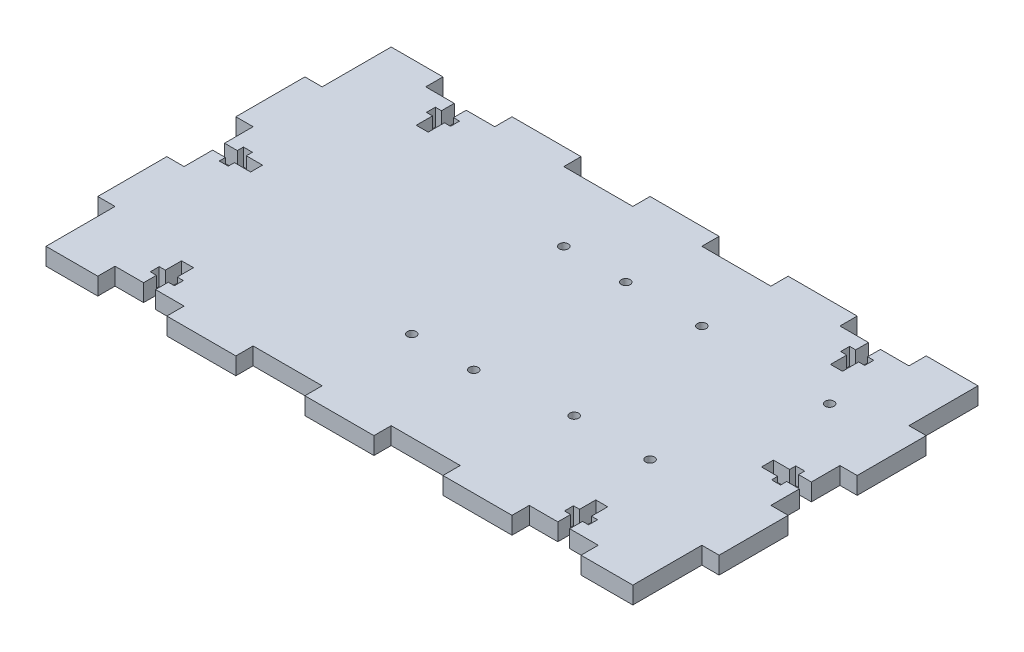
SolidWorks part; units mm, degrees
ref_plane "Front Plane" through (0, 0, 0) normal (0, 0, 1) x (1, 0, 0)
ref_plane "Top Plane" through (0, 0, 0) normal (0, 1, 0) x (1, 0, 0)
ref_plane "Right Plane" through (0, 0, 0) normal (1, 0, 0) x (0, 0, -1)
sketch "Sketch1" plane through (0, 0, 0) normal (0, 1, 0) x (1, 0, 0)
  line L1 (0, 0) -> (228.6, 0)
  line L2 (0, 0) -> (0, 127)
  line L3 (0, 127) -> (228.6, 127)
  line L4 (228.6, 0) -> (228.6, 127)
  dimension "D1" = 127
  dimension "D2" = 228.6
extrude "Boss-Extrude1" add sketch "Sketch1" along normal blind 6.35
sketch "Sketch2" plane through (0, 6.35, 0) normal (0, 1, 0) x (1, 0, 0)
  line L1 (0, 127) -> (6.35, 127)
  line L2 (0, 127) -> (0, 101.6)
  line L3 (0, 101.6) -> (6.35, 101.6)
  line L4 (6.35, 127) -> (6.35, 101.6)
  dimension "D1" = 25.4
  dimension "D2" = 6.35
extrude "Cut-Extrude1" cut sketch "Sketch2" against normal blind 6.35
pattern_linear "LPattern1" count 3 spacing 50.8 along (0, 0, 1) count 2 spacing 222.25 along (1, 0, 0) of "Cut-Extrude1"
sketch "Sketch3" plane through (0, 6.35, 0) normal (0, 1, 0) x (1, 0, 0)
  line L0 (6.35, 0) -> (222.25, 0) construction
  line L1 (25.4, 0) -> (50.8, 0)
  line L2 (25.4, 0) -> (25.4, 6.35)
  line L3 (25.4, 6.35) -> (50.8, 6.35)
  line L4 (50.8, 0) -> (50.8, 6.35)
  line L5 (0, 50.8) -> (0, 25.4) construction
  dimension "D1" = 25.4
  dimension "D2" = 6.35
  dimension "D3" = 25.4
extrude "Cut-Extrude2" cut sketch "Sketch3" against normal blind 6.35
pattern_linear "LPattern2" count 4 spacing 50.8 along (1, 0, 0) count 2 spacing 120.65 along (0, 0, -1) of "Cut-Extrude2"
ref_plane "Plane1" through (0, 0, -63.5) normal (0, 0, 1) x (1, 0, 0)
ref_plane "Plane2" through (114.3, 0, 0) normal (1, 0, 0) x (0, 0, -1)
sketch "Sketch4" plane through (0, 6.35, 0) normal (0, 1, 0) x (1, 0, 0)
  line L0 (222.25, 76.2) -> (222.25, 50.8) construction
  line L1 (222.25, 65.6971) -> (208.28, 65.6971)
  line L2 (222.25, 65.6971) -> (222.25, 61.3029)
  line L3 (222.25, 61.3029) -> (208.28, 61.3029)
  line L4 (208.28, 65.6971) -> (208.28, 61.3029)
  line L5 (228.6, 76.2) -> (222.25, 76.2) construction
  line L7 (214.249, 67.945) -> (217.551, 67.945)
  line L8 (214.249, 67.945) -> (214.249, 59.055)
  line L9 (214.249, 59.055) -> (217.551, 59.055)
  line L10 (217.551, 67.945) -> (217.551, 59.055)
  point P6 (222.25, 63.5)
  point P13 (215.9, 59.055)
  point P14 (217.551, 63.5)
  dimension "D1" = 13.97
  dimension "D2" = 4.3942
  dimension "D3" = 12.7
  dimension "D4" = 3.302
  dimension "D5" = 6.35
  dimension "D6" = 8.89
  dimension "D7" = 12.7
extrude "Cut-Extrude3" cut sketch "Sketch4" against normal blind 8.89 contours L1 L4 L3 L2 | L7 L10 L9 L8
mirror "Mirror1" about plane through (114.3, 0, 0) normal (1, 0, 0) of "Cut-Extrude3"
sketch "Sketch5" plane through (0, 6.35, 0) normal (0, 1, 0) x (1, 0, 0)
  line L0 (50.8, 6.35) -> (25.4, 6.35) construction
  line L1 (35.9029, 6.35) -> (40.2971, 6.35)
  line L2 (35.9029, 6.35) -> (35.9029, 20.32)
  line L3 (35.9029, 20.32) -> (40.2971, 20.32)
  line L4 (40.2971, 6.35) -> (40.2971, 20.32)
  line L5 (50.8, 0) -> (50.8, 6.35) construction
  line L6 (33.655, 14.351) -> (42.545, 14.351)
  line L7 (33.655, 14.351) -> (33.655, 11.049)
  line L8 (33.655, 11.049) -> (42.545, 11.049)
  line L9 (42.545, 14.351) -> (42.545, 11.049)
  point P6 (38.1, 20.32)
  point P12 (38.1, 11.049)
  point P15 (42.545, 12.7)
  dimension "D1" = 13.97
  dimension "D2" = 4.3942
  dimension "D3" = 12.7
  dimension "D4" = 3.302
  dimension "D5" = 8.89
  dimension "D6" = 12.7
  dimension "D7" = 6.35
extrude "Cut-Extrude4" cut sketch "Sketch5" against normal blind 30.48 contours L3 L4 L1 L2 | L7 L8 L9 L6
mirror "Mirror2" about plane through (114.3, 0, 0) normal (1, 0, 0) of "Cut-Extrude4"
mirror "Mirror3" about plane through (0, 0, -63.5) normal (0, 0, 1) of "Mirror2"
sketch "Sketch6" plane through (0, 6.35, 0) normal (0, 1, 0) x (1, 0, 0)
  line L0 (114.3, -21.2715) -> (114.3, 21.2715) construction
  line L1 (152.4, 95.25) -> (200.66, 95.25)
  line L2 (152.4, 95.25) -> (152.4, 43.18)
  line L3 (152.4, 43.18) -> (200.66, 43.18)
  line L4 (200.66, 95.25) -> (200.66, 43.18)
  line L5 (127, 120.65) -> (152.4, 120.65) construction
  dimension "D1" = 52.07
  dimension "D2" = 48.26
  dimension "D3" = 38.1
  dimension "D4" = 25.4
hole_wizard "#4 Clearance Hole1" positions "Sketch9" profile "Sketch8" hole size "#4" standard "ANSI Inch"
sketch "Sketch9" plane through (0, 6.35, 0) normal (0, 1, 0) x (1, 0, 0)
  line L0 (200.66, 95.25) -> (200.66, 43.18) construction
  line L1 (152.4, 95.25) -> (200.66, 95.25) construction
  line L2 (152.4, 43.18) -> (200.66, 43.18) construction
  line L3 (152.4, 95.25) -> (152.4, 43.18) construction
  point P0 (152.4, 95.25)
  point P2 (200.66, 93.98)
  point P4 (185.42, 43.18)
  point P6 (157.48, 43.18)
  dimension "D1" = 1.27
  dimension "D2" = 5.08
  dimension "D3" = 15.24
sketch "Sketch8" plane through (152.4, 6.35, -95.25) normal (1, 0, 0) x (0, 0, 1)
  line L0 (0, 0) -> (0, 11.1406)
  line L1 (0, 11.1406) -> (1.6319, 10.16)
  line L2 (1.6319, 10.16) -> (1.6319, 0)
  line L5 (1.6319, 0) -> (0, 0)
  line L10 (0, 11.1406) -> (-1.632, 10.16) construction
  line L11 (0, -6.35) -> (0, 107.95) construction
  dimension "Hole Dia." = 3.2639
  dimension "Hole Depth" = 10.16
  dimension "Drill Angle" = 118
sketch "Sketch10" plane through (0, 6.35, 0) normal (0, 1, 0) x (1, 0, 0)
  line L0 (0, 101.6) -> (0, 76.2) construction
  line L1 (101.6, 95.25) -> (124.4092, 95.25)
  line L2 (101.6, 95.25) -> (101.6, 39.3192)
  line L3 (101.6, 39.3192) -> (124.4092, 39.3192)
  line L4 (124.4092, 95.25) -> (124.4092, 39.3192)
  circle A0 centre (152.4, 95.25) radius 1.6319 construction
  point P6 (0, 88.9)
  dimension "D1" = 22.8092
  dimension "D2" = 55.9308
  dimension "D3" = 0
  dimension "D4" = 101.6
hole_wizard "#4 Clearance Hole2" positions "Sketch12" profile "Sketch11" hole size "#4" standard "ANSI Inch"
sketch "Sketch12" plane through (0, 6.35, 0) normal (0, 1, 0) x (1, 0, 0)
  point P0 (101.6, 95.25)
  point P3 (124.4092, 95.25)
  point P6 (124.4092, 39.3192)
  point P9 (101.6, 39.3192)
sketch "Sketch11" plane through (101.6, 6.35, -95.25) normal (1, 0, 0) x (0, 0, 1)
  line L0 (0, 0) -> (0, 11.1406)
  line L1 (0, 11.1406) -> (1.6319, 10.16)
  line L2 (1.6319, 10.16) -> (1.6319, 0)
  line L5 (1.6319, 0) -> (0, 0)
  line L10 (0, 11.1406) -> (-1.6319, 10.16) construction
  line L11 (0, -6.35) -> (0, 107.95) construction
  dimension "Hole Dia." = 3.2639
  dimension "Hole Depth" = 10.16
  dimension "Drill Angle" = 118
